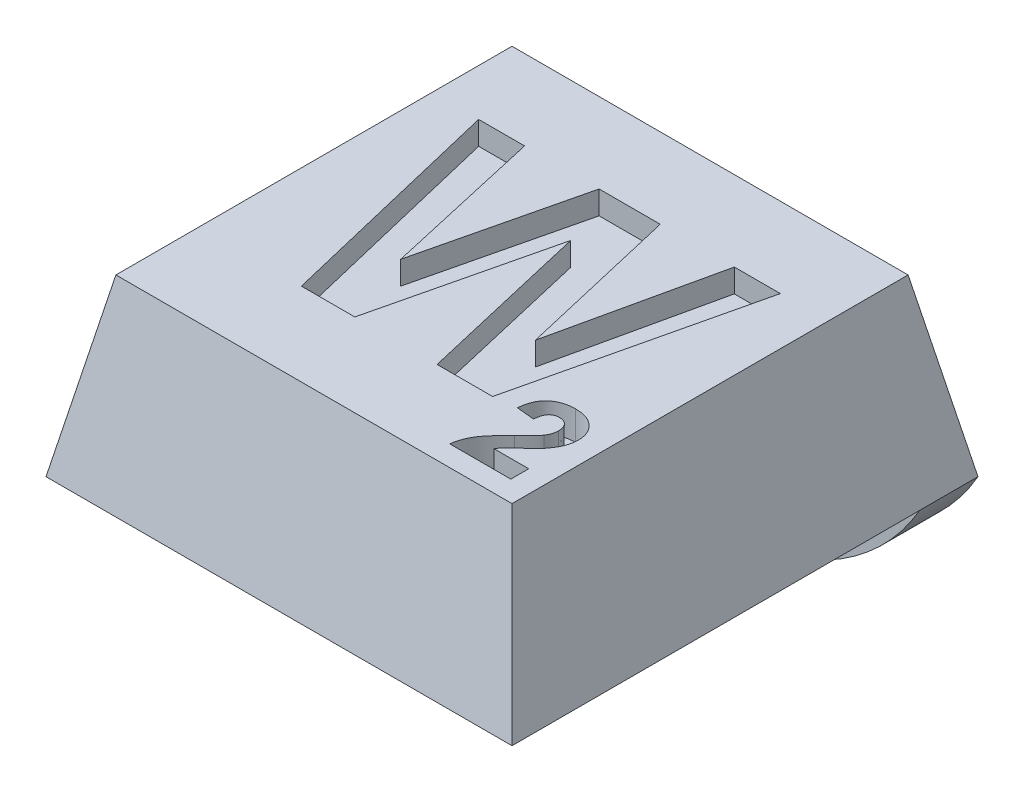
SolidWorks part; units mm, degrees
ref_plane "Front Plane" through (0, 0, 0) normal (0, 0, 1) x (1, 0, 0)
ref_plane "Top Plane" through (0, 0, 0) normal (0, 1, 0) x (1, 0, 0)
ref_plane "Right Plane" through (0, 0, 0) normal (1, 0, 0) x (0, 0, -1)
sketch "Sketch1" plane through (0, 0, 0) normal (0, 1, 0) x (1, 0, 0)
  line L1 (0, 0) -> (8, 0)
  line L2 (0, 0) -> (0, 8)
  line L3 (0, 8) -> (8, 8)
  line L4 (8, 0) -> (8, 8)
  dimension "D1" = 8
  dimension "D2" = 8
extrude "Boss-Extrude1" add sketch "Sketch1" along normal blind 3
sketch "Sketch2" plane through (0, 0, 0) normal (0, 0, 1) x (1, 0, 0)
  line L0 (0, 0) -> (0.6, 3)
  line L1 (0, 3) -> (8, 3) construction
  line L2 (0.6, 3) -> (0, 3)
  line L3 (0, 3) -> (0, 0)
  line L4 (8, 0) -> (7.4, 3)
  line L5 (7.4, 3) -> (8, 3)
  line L6 (8, 3) -> (8, 0)
  dimension "D1" = 0.6
  dimension "D2" = 0.6
extrude "Cut-Extrude1" cut sketch "Sketch2" against normal through all both and the other way through all
sketch "Sketch3" plane through (0, 0, 0) normal (1, 0, 0) x (0, 0, -1)
  line L0 (0, 0) -> (0.6, 3)
  line L1 (8, 3) -> (0, 3) construction
  line L2 (0.6, 3) -> (0, 3)
  line L3 (0, 3) -> (0, 0)
  line L4 (8, 3) -> (7.4, 3)
  line L5 (7.4, 3) -> (8, 0)
  line L6 (8, 3) -> (8, 0)
  dimension "D1" = 0.6
  dimension "D2" = 0.6
extrude "Cut-Extrude2" cut sketch "Sketch3" along normal blind 11
sketch "Sketch4" plane through (0, 0, 0) normal (0, -1, 0) x (1, 0, 0)
  line L0 (8, 0) -> (8, -8) construction
  line L3 (0, 0) -> (8, 0) construction
  circle A0 centre (4, -3.75) radius 1.75
  dimension "D1" = 3.5
  dimension "D2" = 4
  dimension "D3" = 3.75
extrude "Cut-Extrude3" cut sketch "Sketch4" against normal blind 0.4
sketch "Sketch5" plane through (0, 0, 0) normal (0, -1, 0) x (1, 0, 0)
  line L0 (8, 0) -> (8, -8) construction
  line L1 (0, -8) -> (8, -8)
  line L2 (0, -8) -> (0, -7)
  line L3 (0, -7) -> (8, -7)
  line L4 (8, -8) -> (8, -7)
  dimension "D1" = 1
extrude "Boss-Extrude2" add sketch "Sketch5" along normal blind 2
fillet "Fillet1" radius 4 2 edges at (8, -2, -7.5) (0, -2, -7.5)
sketch "Sketch6" plane through (0, 3, 0) normal (0, 1, 0) x (1, 0, 0)
  text T0 "W" font "Arial" height 4
extrude "Cut-Extrude4" cut sketch "Sketch6" against normal blind 0.4
sketch "Sketch7" plane through (0, 3, 0) normal (0, 1, 0) x (1, 0, 0)
  text T0 "2" font "Arial" height 1.6
extrude "Cut-Extrude5" cut sketch "Sketch7" against normal blind 0.5
